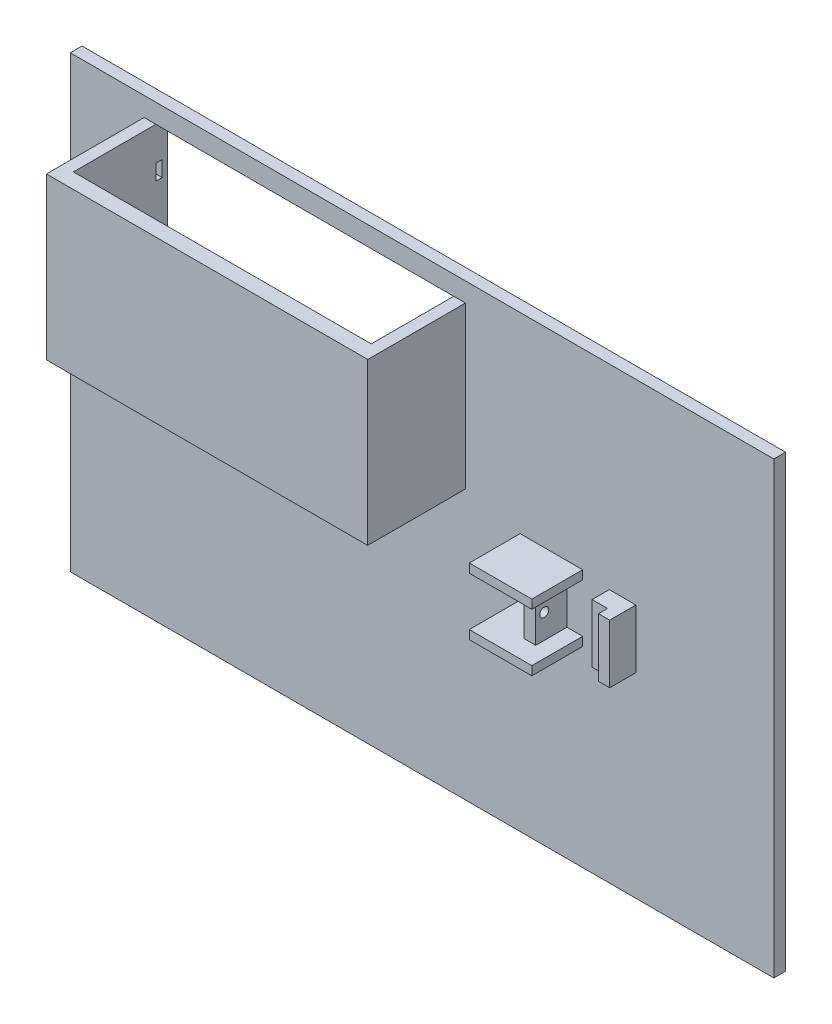
SolidWorks part; units mm, degrees
ref_plane "前视基准面" through (0, 0, 0) normal (0, 0, 1) x (1, 0, 0)
ref_plane "上视基准面" through (0, 0, 0) normal (0, 1, 0) x (1, 0, 0)
ref_plane "右视基准面" through (0, 0, 0) normal (1, 0, 0) x (0, 0, -1)
sketch "草图1" plane through (0, 0, 0) normal (0, 0, 1) x (1, 0, 0)
  line L1 (-90, 57.5) -> (90, 57.5)
  line L2 (-90, 57.5) -> (-90, -57.5)
  line L3 (-90, -57.5) -> (90, -57.5)
  line L4 (90, 57.5) -> (90, -57.5)
  line L5 (-90, 57.5) -> (90, -57.5) construction
  line L6 (-90, -57.5) -> (90, 57.5) construction
  point P0 (0, 0)
  dimension "D1" = 115
  dimension "D2" = 180
extrude "凸台-拉伸1" add sketch "草图1" along normal blind 3
sketch "草图7" plane through (0, 0, 0) normal (0, 0, -1) x (-1, 0, 0)
  line L0 (-90, 57.5) -> (90, 57.5) construction
  line L1 (-8.1, 52.6) -> (68.1, 52.6)
  line L2 (-8.1, 52.6) -> (-8.1, 11.4)
  line L3 (-8.1, 11.4) -> (68.1, 11.4)
  line L4 (68.1, 52.6) -> (68.1, 11.4)
  line L5 (90, 57.5) -> (90, -57.5) construction
  dimension "D1" = 41.2
  dimension "D2" = 76.2
  dimension "D3" = 4.9
  dimension "D4" = 21.9
extrude "电池位切除-拉伸3" cut sketch "草图7" against normal up to next
sketch "草图4" plane through (0, 0, 0) normal (0, 0, -1) x (-1, 0, 0)
  line L0 (68.1, 11.4) -> (68.1, 52.6) construction
  line L5 (68.1, 32) -> (94.8483, 32) construction
  line L10 (83.2374, -53.4277) -> (79.3374, -53.4277) construction
  line L11 (83.2374, -49.6277) -> (83.2374, -53.4277) construction
  line L12 (79.3374, -49.6277) -> (83.2374, -49.6277) construction
  line L13 (68.1, 20) -> (68.1, 24)
  line L20 (72.1, 20) -> (68.1, 20)
  line L21 (72.1, 24) -> (72.1, 20)
  line L22 (68.1, 24) -> (72.1, 24)
  line L29 (68.1, 40) -> (72.1, 40)
  line L30 (72.1, 40) -> (72.1, 44)
  line L31 (72.1, 44) -> (68.1, 44)
  line L32 (68.1, 44) -> (68.1, 40)
  point P6 (70.1, 40)
  dimension "D1" = 4
  dimension "D2" = 4
  dimension "D3" = 8
extrude "切除-拉伸2" cut sketch "草图4" along normal blind 1.6 from surface starting at face at (-30, 32, 3)
sketch "草图8" plane through (0, 0, 3) normal (0, 0, 1) x (1, 0, 0)
  line L0 (-68.1, 11.4) -> (-68.1, 20) construction
  line L1 (11.1, 11.4) -> (8.1, 11.4)
  line L2 (11.1, 11.4) -> (11.1, 52.6)
  line L3 (11.1, 52.6) -> (8.1, 52.6)
  line L4 (8.1, 11.4) -> (8.1, 52.6)
  line L5 (-68.1, 11.4) -> (-71.1, 11.4)
  line L6 (-68.1, 11.4) -> (-68.1, 52.6)
  line L7 (-68.1, 52.6) -> (-71.1, 52.6)
  line L8 (-71.1, 11.4) -> (-71.1, 52.6)
  line L9 (-68.1, 52.6) -> (8.1, 52.6) construction
  line L10 (8.1, 11.4) -> (-68.1, 11.4) construction
  line L11 (8.1, 52.6) -> (8.1, 11.4) construction
  dimension "D1" = 3
extrude "凸台-拉伸2" add sketch "草图8" along normal blind 25
sketch "草图9" plane through (0, 0, 28) normal (0, 0, 1) x (1, 0, 0)
  line L1 (11.1, 11.4) -> (-71.1, 11.4)
  line L2 (11.1, 11.4) -> (11.1, 52.6)
  line L3 (11.1, 52.6) -> (-71.1, 52.6)
  line L4 (-71.1, 11.4) -> (-71.1, 52.6)
extrude "凸台-拉伸3" add sketch "草图9" against normal blind 3.9
sketch "草图10" plane through (0, 0, 3) normal (0, 0, 1) x (1, 0, 0)
  line L0 (47.9, 5.35) -> (47.9, 67.7) construction
  line L1 (54.7, -7.5) -> (47.9, -7.5)
  line L2 (54.7, -7.5) -> (54.7, 7.5)
  line L3 (54.7, 7.5) -> (47.9, 7.5)
  line L4 (47.9, -7.5) -> (47.9, 7.5)
  line L5 (51.7, 0.7) -> (51.7, -61.65) construction
  line L6 (71.1, -9.5) -> (15, -9.5) construction
  line L7 (15, 9.5) -> (71.1, 9.5) construction
  dimension "D1" = 3
  dimension "D2" = 2
  dimension "D3" = 2
extrude "变速杆凸台-拉伸4" add sketch "草图10" along normal offset from surface (4.4 mm away) 0.1
sketch "草图11" plane through (0, 0, 7.4) normal (0, 0, 1) x (1, 0, 0)
  line L0 (54.7, -7.5) -> (47.9, -7.5) construction
  line L1 (54.7, -7.5) -> (51.85, -7.5)
  line L2 (54.7, -7.5) -> (54.7, 7.5)
  line L3 (54.7, 7.5) -> (51.85, 7.5)
  line L4 (51.85, -7.5) -> (51.85, 7.5)
  line L5 (54.7, 7.5) -> (54.7, -7.5) construction
  line L6 (47.9, 7.5) -> (54.7, 7.5) construction
  line L7 (51.7, 67.7) -> (51.7, 5.35) construction
  dimension "D1" = 0.15
extrude "变速杆前档凸台-拉伸5" add sketch "草图11" along normal blind 2.3
sketch "草图12" plane through (0, 0, 3) normal (0, 0, 1) x (1, 0, 0)
  line L0 (39.5974, -6.096) -> (37.2352, -6.096) construction
  line L1 (37.0852, -8.5) -> (25.0852, -8.5)
  line L3 (34.0852, -6.246) -> (25.0852, -6.246)
  line L4 (25.0852, -8.5) -> (25.0852, -6.246)
  line L5 (34.0852, 6.246) -> (25.0852, 6.246)
  line L7 (37.0852, 8.5) -> (25.0852, 8.5)
  line L8 (25.0852, 6.246) -> (25.0852, 8.5)
  line L9 (37.2352, 6.096) -> (39.5974, 6.096) construction
  line L10 (15, 9.5) -> (71.1, 9.5) construction
  line L11 (71.1, -9.5) -> (15, -9.5) construction
  line L13 (37.2352, -0.635) -> (37.2352, -5.461) construction
  line L15 (37.0852, -6.246) -> (37.0852, 6.246)
  line L17 (34.0852, -6.246) -> (34.0852, 6.246)
  line L19 (37.0852, 8.5) -> (41.0852, 8.5)
  line L21 (37.0852, 6.246) -> (41.0852, 6.246)
  line L22 (41.0852, 8.5) -> (41.0852, 6.246)
  line L23 (37.0852, -6.246) -> (41.0852, -6.246)
  line L25 (37.0852, -8.5) -> (41.0852, -8.5)
  line L26 (41.0852, -6.246) -> (41.0852, -8.5)
  point P12 (38.4163, 6.096)
  dimension "D1" = 0.15
  dimension "D2" = 0.15
  dimension "D3" = 1
  dimension "D4" = 1
  dimension "D5" = 4
  dimension "D7" = 0.15
  dimension "D8" = 3
  dimension "D9" = 9
extrude "变速舵机底座凸台-拉伸6" add sketch "草图12" along normal offset from surface (8.004 mm away) 0.1
sketch "草图13" plane through (0, 0, 11.004) normal (0, 0, 1) x (1, 0, 0)
  line L0 (25.0852, -8.5) -> (41.0852, -8.5) construction
  line L1 (25.0852, -8.5) -> (41.0852, -8.5)
  line L2 (34.0852, -6.246) -> (25.0852, -6.246) construction
  line L3 (34.0852, -6.246) -> (25.0852, -6.246)
  line L4 (41.0852, -8.5) -> (41.0852, -6.246) construction
  line L5 (41.0852, -8.5) -> (41.0852, -6.246)
  line L6 (25.0852, -6.246) -> (25.0852, -8.5) construction
  line L7 (25.0852, -6.246) -> (25.0852, -8.5)
  line L8 (41.0852, 8.5) -> (25.0852, 8.5) construction
  line L9 (41.0852, 8.5) -> (25.0852, 8.5)
  line L10 (25.0852, 8.5) -> (25.0852, 6.246) construction
  line L11 (25.0852, 8.5) -> (25.0852, 6.246)
  line L12 (25.0852, 6.246) -> (34.0852, 6.246) construction
  line L13 (25.0852, 6.246) -> (34.0852, 6.246)
  line L14 (41.0852, 6.246) -> (41.0852, 8.5) construction
  line L15 (41.0852, 6.246) -> (41.0852, 8.5)
  line L16 (34.0852, -6.246) -> (41.0852, -6.246)
  line L17 (34.0852, 6.246) -> (41.0852, 6.246)
extrude "变速舵机卡位凸台-拉伸7" add sketch "草图13" along normal blind 5
sketch "草图15" plane through (34.0852, 0, 0) normal (-1, 0, 0) x (0, 0, 1)
  circle A0 centre (8.818, 0) radius 1.15
  dimension "D1" = 2.3
extrude "变速舵机螺丝孔切除-拉伸7" cut sketch "草图15" against normal up to next
